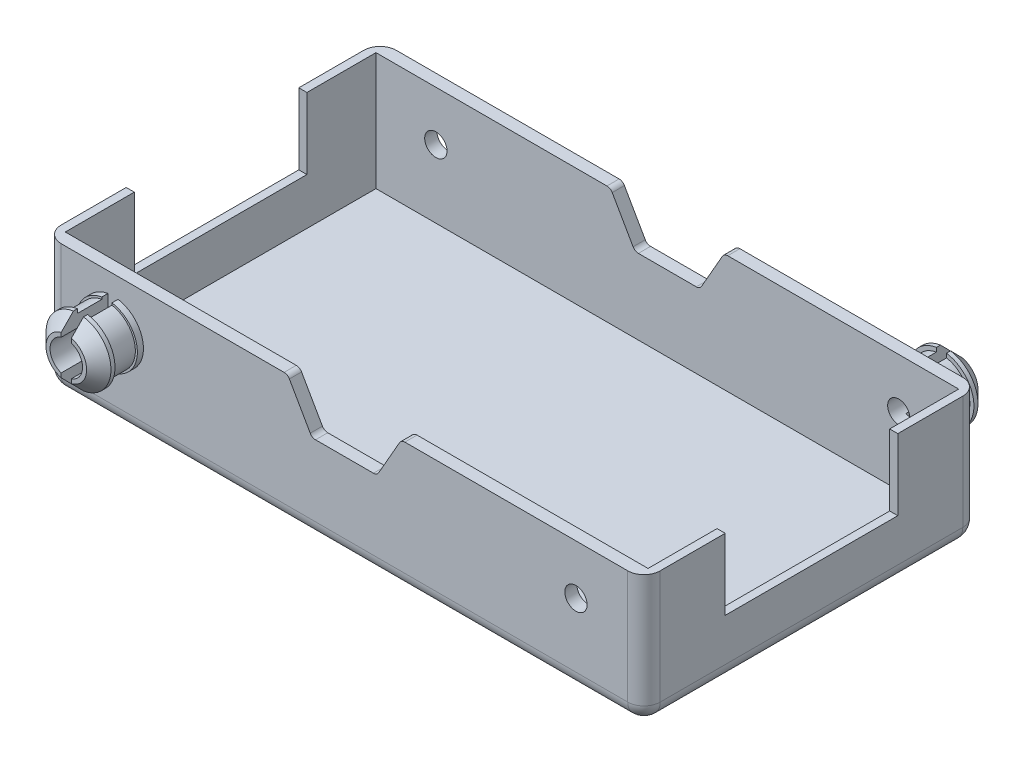
SolidWorks part; units mm, degrees
ref_plane "Front Plane" through (0, 0, 0) normal (0, 0, 1) x (1, 0, 0)
ref_plane "Top Plane" through (0, 0, 0) normal (0, 1, 0) x (1, 0, 0)
ref_plane "Right Plane" through (0, 0, 0) normal (1, 0, 0) x (0, 0, -1)
sketch "Sketch1" plane through (0, 0, 0) normal (0, 1, 0) x (1, 0, 0)
  line L1 (0, 0) -> (147.5, 0)
  line L2 (0, 0) -> (0, 82.5)
  line L3 (0, 82.5) -> (147.5, 82.5)
  line L4 (147.5, 0) -> (147.5, 82.5)
  dimension "D1" = 147.5
  dimension "D2" = 82.5
extrude "Boss-Extrude1" add sketch "Sketch1" along normal blind 32
shell "Shell1" thickness 3 removed face at (73.75, 32, -41.25)
fillet "Fillet1" radius 4 8 edges at (73.75, 0, 0) (147.5, 0, -41.25) (73.75, 0, -82.5) (0, 0, -41.25) (147.5, 16, -82.5) (147.5, 16, 0) (0, 16, -82.5) (0, 16, 0)
sketch "Sketch4" plane through (3, 0, 0) normal (1, 0, 0) x (0, 0, -1)
  line L4 (3, 3) -> (79.5, 3)
  line L5 (79.5, 3) -> (79.5, 32)
  line L6 (79.5, 32) -> (3, 32)
  line L7 (79.5, 3) -> (79.5, 32)
  line L8 (3, 3) -> (79.5, 3)
  line L10 (79.5, 32) -> (3, 32)
  line L12 (3, 32) -> (3, 3)
  line L13 (3, 32) -> (3, 3)
  dimension "D1" = 0
extrude "Cut-Extrude1" cut sketch "Sketch4" along normal offset from surface (143.5 mm away) 2 from offset 1 up to face at (147.5, 18, -41.25) offset against normal yes
sketch "Sketch5" plane through (147.5, 0, 0) normal (1, 0, 0) x (0, 0, -1)
  line L0 (4, 32) -> (78.5, 32) construction
  line L1 (20, 32) -> (62.5, 32)
  line L2 (20, 32) -> (20, 14.5)
  line L3 (20, 14.5) -> (62.5, 14.5)
  line L4 (62.5, 32) -> (62.5, 14.5)
  line L6 (78.5, 0) -> (4, 0) construction
  line L7 (41.25, 4) -> (41.25, 46.3808) construction
  line L8 (4, 4) -> (78.5, 4) construction
  point P12 (41.25, 14.5)
  dimension "D1" = 42.5
  dimension "D2" = 14.5
extrude "Cut-Extrude2" cut sketch "Sketch5" against normal up to surface (147.5 mm away) up to face at (0, 18, -41.25)
sketch "Sketch6" plane through (0, 0, 0) normal (0, 0, 1) x (1, 0, 0)
  line L0 (4, 32) -> (143.5, 32) construction
  line L1 (65.75, 21.5) -> (81.75, 21.5)
  line L4 (81.75, 21.5) -> (81.75, 32) construction
  line L5 (65.75, 21.5) -> (73.75, 32) construction
  line L6 (73.75, 32) -> (81.75, 21.5) construction
  line L7 (81.75, 21.5) -> (87.75, 32)
  line L8 (65.75, 21.5) -> (59.75, 32)
  line L9 (59.75, 32) -> (87.75, 32)
  point P0 (73.75, 32)
  dimension "D1" = 8
  dimension "D2" = 14
  dimension "D3" = 14
  dimension "D4" = 10.5
extrude "Cut-Extrude3" cut sketch "Sketch6" against normal up to surface (82.5 mm away) up to face at (73.75, 18, -82.5)
fillet "Fillet2" radius 1.5 8 edges at (87.75, 32, -81) (81.75, 21.5, -81) (59.75, 32, -81) (65.75, 21.5, -81) (87.75, 32, -1.5) (81.75, 21.5, -1.5) (59.75, 32, -1.5) (65.75, 21.5, -1.5)
sketch "Sketch7" plane through (0, 0, 0) normal (0, 0, 1) x (1, 0, 0)
  line L1 (4, 4) -> (143.5, 4) construction
  line L3 (73.75, 4) -> (73.75, 37.0086) construction
  circle A0 centre (16.75, 19.75) radius 2.75
  circle A2 centre (130.75, 19.75) radius 2.75
  point P2 (16.75, 17)
  point P13 (0, 0)
  point P14 (0, 0)
  dimension "D1" = 5.5
  dimension "D2" = 13
  dimension "D5" = 114
extrude "Cut-Extrude4" cut sketch "Sketch7" against normal up to surface (82.5 mm away) up to face at (73.75, 23.8333, -82.5)
sketch "Sketch8" plane through (0, 0, 0) normal (0, 0, 1) x (1, 0, 0)
  line L0 (16.75, 19.75) -> (16.75, 30.7129) construction
  line L1 (15.5, 32) -> (15.5, 0) construction
  line L2 (4, 32) -> (58.8795, 32) construction
  line L3 (143.5, 0) -> (4, 0) construction
  line L4 (18, 32) -> (18, 0) construction
  circle A0 centre (16.75, 19.75) radius 8
  circle A2 centre (16.75, 19.75) radius 6
  circle A4 centre (16.75, 19.75) radius 5
  dimension "D1" = 16
  dimension "D2" = 3
  dimension "D3" = 1
  dimension "D4" = 1.25
  dimension "D5" = 2.5
sketch "Sketch9" plane through (0, 0, 0) normal (0, 0, 1) x (1, 0, 0)
  circle A0 centre (16.75, 19.75) radius 7.5
  circle A1 centre (16.75, 19.75) radius 2.75 construction
  circle A2 centre (16.75, 19.75) radius 2.75
  dimension "D1" = 15
extrude "Boss-Extrude3" add sketch "Sketch9" along normal blind 1.5
ref_axis "Axis1" through (16.75, 19.75, 0) along (0, 0, 1)
ref_plane "Plane1" through (16.75, 0, 0) normal (-1, 0, 0) x (0, 0, 1)
sketch "Sketch10" plane through (16.75, 0, 0) normal (-1, 0, 0) x (0, 0, 1)
  line L0 (0, 19.75) -> (33.8718, 19.75) construction
  line L1 (0, 32) -> (0, 0) construction
  line L2 (0, 19.75) -> (54.7881, 19.75) construction
  line L4 (11.5, 24.75) -> (8.5, 27.75)
  line L5 (8.5, 27.75) -> (7.5, 27.75)
  line L6 (7.5, 27.75) -> (7.5, 26.75)
  line L10 (1.5, 23.75) -> (11.5, 23.75)
  line L11 (11.5, 24.75) -> (11.5, 29.847) construction
  line L12 (8.5, 27.75) -> (15.1697, 21.0803) construction
  line L13 (11.5, 24.75) -> (11.5, 23.75)
  line L14 (7.5, 26.75) -> (1.5, 26.75)
  line L15 (1.5, 12.25) -> (1.5, 27.25) construction
  line L16 (1.5, 26.75) -> (1.5, 23.75)
  dimension "D1" = 1
  dimension "D2" = 1
  dimension "D3" = 4
  dimension "D4" = 135
  dimension "D5" = 1
  dimension "D6" = 8
  dimension "D7" = 10
revolve "Revolve1" add sketch "Sketch10" angle 360 about axis through (16.75, 19.75, 0) along (0, 0, 1)
sketch "Sketch11" plane through (0, 0, 0) normal (0, 0, 1) x (1, 0, 0)
  line L2 (15.5, 32) -> (15.5, 0) construction
  line L3 (15.5, 27.75) -> (18, 27.75)
  line L4 (18, 32) -> (18, 0) construction
  line L5 (18, 27.75) -> (18, 11.75)
  line L6 (18, 11.75) -> (15.5, 11.75)
  line L7 (15.5, 11.75) -> (15.5, 27.75)
extrude "Cut-Extrude5" cut sketch "Sketch11" along normal up to surface (11.5 mm away) up to face at (11.75, 19.75, 11.5)
ref_plane "Plane2" through (73.75, 0, 0) normal (-1, 0, 0) x (0, 0, 1)
ref_plane "Plane3" through (0, 0, -41.25) normal (0, 0, 1) x (1, 0, 0)
ref_plane "Plane4" through (57.5, 0, -57.5) normal (-0.7071, 0, 0.7071) x (0.7071, 0, 0.7071)
mirror "Mirror2" about plane through (73.75, 0, 0) normal (-1, 0, 0) of "Cut-Extrude5", "Revolve1", "Boss-Extrude3" second plane through (0, 0, -41.25) second plane normal (0, 0, 1)
sketch "Sketch12" plane through (0, 0, -82.5) normal (0, 0, -1) x (-1, 0, 0)
  line L0 (-4, 4) -> (-4, 32) construction
  line L1 (-29.2385, 30.4129) -> (-4, 30.4129)
  line L2 (-29.2385, 30.4129) -> (-29.2385, 7.9541)
  line L3 (-29.2385, 7.9541) -> (-4, 7.9541)
  line L4 (-4, 30.4129) -> (-4, 7.9541)
extrude "Cut-Extrude6" cut sketch "Sketch12" along normal up to surface (11.5 mm away) up to face at (13.875, 19.75, -94)
sketch "Sketch13" plane through (0, 0, 0) normal (0, 0, 1) x (1, 0, 0)
  line L0 (143.5, 4) -> (143.5, 32) construction
  line L1 (61.9909, 29.7891) -> (143.5, 29.7891)
  line L2 (61.9909, 29.7891) -> (61.9909, 10.4496)
  line L3 (61.9909, 10.4496) -> (143.5, 10.4496)
  line L4 (143.5, 29.7891) -> (143.5, 10.4496)
extrude "Cut-Extrude7" cut sketch "Sketch13" along normal up to surface (11.5 mm away)
